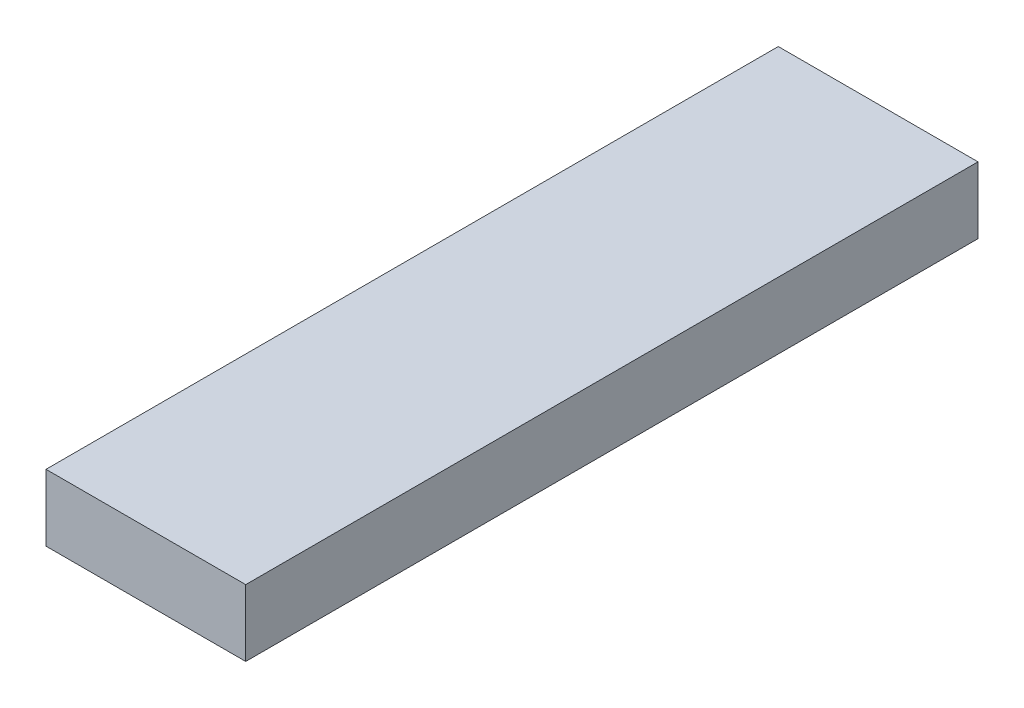
SolidWorks part; units mm, degrees
ref_plane "Front Plane" through (0, 0, 0) normal (0, 0, 1) x (1, 0, 0)
ref_plane "Top Plane" through (0, 0, 0) normal (0, 1, 0) x (1, 0, 0)
ref_plane "Right Plane" through (0, 0, 0) normal (1, 0, 0) x (0, 0, -1)
sketch "Sketch1" plane through (0, 0, 0) normal (0, 0, 1) x (1, 0, 0)
  line L1 (-45, -15) -> (45, -15)
  line L2 (-45, -15) -> (-45, 15)
  line L3 (-45, 15) -> (45, 15)
  line L4 (45, -15) -> (45, 15)
  line L5 (-45, -15) -> (45, 15) construction
  line L6 (-45, 15) -> (45, -15) construction
  point P0 (0, 0)
  dimension "D1" = 90
  dimension "D2" = 30
extrude "Boss-Extrude1" add sketch "Sketch1" along normal mid plane 330
